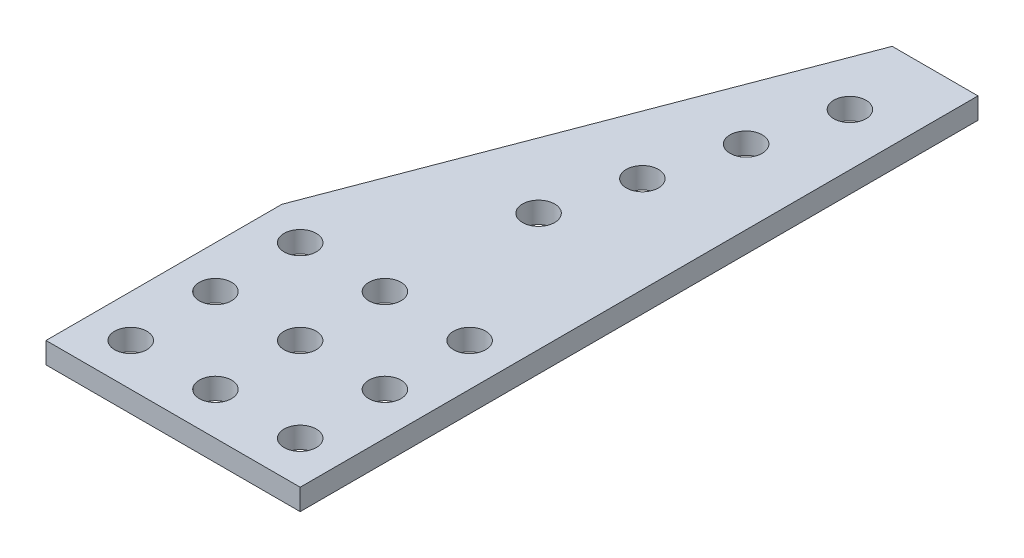
SolidWorks part; units mm, degrees
ref_plane "Front Plane" through (0, 0, 0) normal (0, 0, 1) x (1, 0, 0)
ref_plane "Top Plane" through (0, 0, 0) normal (0, 1, 0) x (1, 0, 0)
ref_plane "Right Plane" through (0, 0, 0) normal (1, 0, 0) x (0, 0, -1)
sketch "Sketch1" plane through (0, 0, 0) normal (0, 1, 0) x (1, 0, 0)
  line L7 (0, 0) -> (38.1, 0)
  line L8 (0, 0) -> (0, 101.6)
  line L9 (0, 101.6) -> (38.1, 101.6)
  line L10 (38.1, 0) -> (38.1, 101.6)
  dimension "D1" = 38.1
  dimension "D2" = 101.6
extrude "Boss-Extrude1" add sketch "Sketch1" along normal blind 3.175
sketch "Sketch2" plane through (0, 3.175, 0) normal (0, 1, 0) x (1, 0, 0)
  line L0 (0, 0) -> (38.1, 0) construction
  line L1 (0, 101.6) -> (0, 0) construction
  circle A0 centre (6.35, 6.35) radius 2.413
  circle A1 centre (19.05, 6.35) radius 2.413
  circle A2 centre (31.75, 6.35) radius 2.413
  circle A4 centre (6.35, 19.05) radius 2.413
  circle A5 centre (19.05, 19.05) radius 2.413
  circle A6 centre (31.75, 19.05) radius 2.413
  circle A7 centre (6.35, 31.75) radius 2.413
  circle A8 centre (19.05, 31.75) radius 2.413
  circle A9 centre (31.75, 31.75) radius 2.413
  dimension "D1" = 6.35
  dimension "D2" = 6.35
  dimension "D3" = 12.7
  dimension "D4" = 12.7
  dimension "D5" = 4.826
  dimension "D6" = 3
extrude "Cut-Extrude1" cut sketch "Sketch2" against normal through all
sketch "Sketch4" plane through (0, 3.175, 0) normal (0, 1, 0) x (1, 0, 0)
  line L3 (38.1, 101.6) -> (0, 101.6) construction
  line L5 (0, 101.6) -> (0, 0) construction
  line L10 (25.2398, 101.6) -> (0, 35.3562)
  line L15 (0, 35.3562) -> (0, 101.6)
  line L16 (0, 101.6) -> (25.2398, 101.6)
extrude "Cut-Extrude3" cut sketch "Sketch4" against normal through all
sketch "Sketch3" plane through (0, 3.175, 0) normal (0, 1, 0) x (1, 0, 0)
  line L0 (30.2662, 90.232) -> (20.4052, 53.4303) construction
  line L1 (0, 0) -> (38.1, 0) construction
  line L6 (0, 0) -> (38.1, 0) construction
  line L7 (0, 35.3562) -> (0, 0) construction
  circle A0 centre (30.2662, 90.232) radius 2.413
  circle A1 centre (26.9792, 77.9648) radius 2.413
  circle A2 centre (23.6922, 65.6975) radius 2.413
  circle A3 centre (20.4052, 53.4303) radius 2.413
  dimension "D2" = 4.826
  dimension "D3" = 12.7
  dimension "D4" = 12.7
  dimension "D6" = 90.232
  dimension "D7" = 30.2662
  dimension "D1" = 75
  dimension "D5" = 12.7
extrude "Cut-Extrude2" cut sketch "Sketch3" against normal through all
